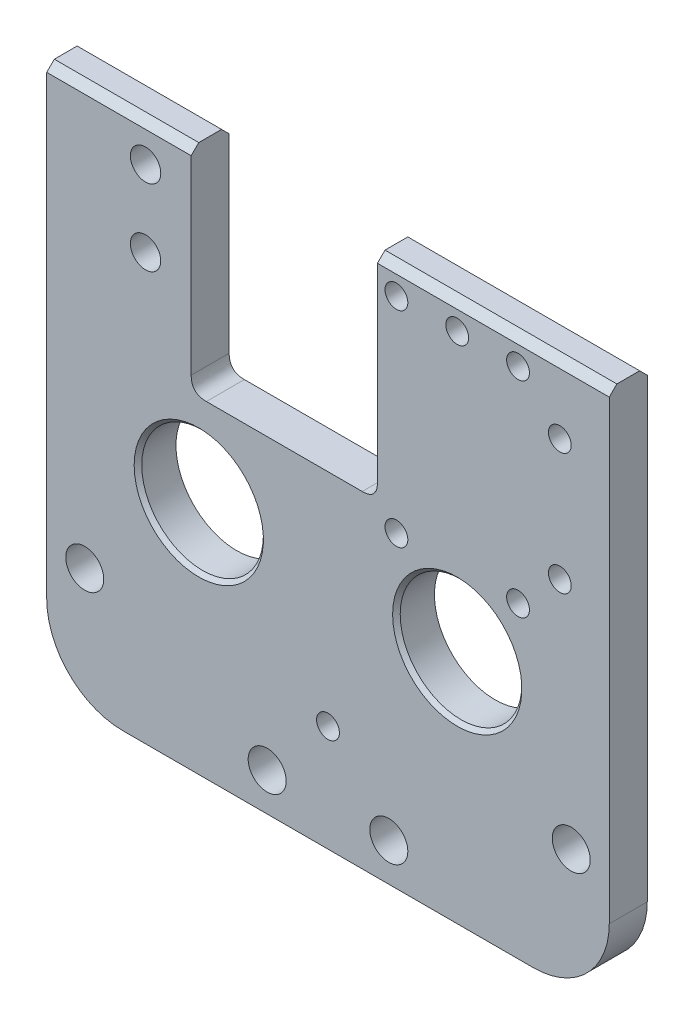
SolidWorks part; units mm, degrees
material "Stop 1060"
ref_plane "Płaszczyzna przednia" through (0, 0, 0) normal (0, 0, 1) x (1, 0, 0)
ref_plane "Płaszczyzna górna" through (0, 0, 0) normal (0, 1, 0) x (1, 0, 0)
ref_plane "Płaszczyzna prawa" through (0, 0, 0) normal (1, 0, 0) x (0, 0, -1)
sketch "Szkic1" plane through (0, 0, 0) normal (0, 0, 1) x (1, 0, 0)
  line L2 (34, 36) -> (34, -35)
  line L3 (34, -35) -> (-20, -35)
  line L6 (-20, -35) -> (-20, 36)
  line L7 (-20, 36) -> (34, 36)
  dimension "D1" = 71
  dimension "D2" = 20
  dimension "D3" = 54
  dimension "D4" = 36
extrude "Dodanie-wyciągnięcie1" add sketch "Szkic1" along normal blind 5
sketch "Szkic2" plane through (0, 0, 5) normal (0, 0, 1) x (1, 0, 0)
  line L1 (-20, 36) -> (3.5, 36)
  line L2 (-20, 36) -> (-20, 8)
  line L3 (-20, 8) -> (3.5, 8)
  line L4 (3.5, 36) -> (3.5, 8)
  dimension "D1" = 28
  dimension "D2" = 23.5
extrude "Wytnij-wyciągnięcie1" cut sketch "Szkic2" against normal blind 5
sketch "Szkic3" plane through (0, 0, 0) normal (0, 0, -1) x (-1, 0, 0)
  line L0 (-3.5, 8) -> (-3.5, 36) construction
  line L1 (-3.5, 30.5) -> (-24.5, 30.5)
  line L2 (-3.5, 30.5) -> (-3.5, 9.5)
  line L3 (-3.5, 9.5) -> (-24.5, 9.5)
  line L4 (-24.5, 30.5) -> (-24.5, 9.5)
  line L5 (-34, 36) -> (-3.5, 36) construction
  dimension "D1" = 5.5
  dimension "D2" = 21
  dimension "D3" = 21
extrude "Wytnij-wyciągnięcie2" cut sketch "Szkic3" against normal blind 3
sketch "Szkic4" plane through (0, 0, 5) normal (0, 0, 1) x (1, 0, 0)
  line L0 (3.5, 8) -> (3.5, 36) construction
  line L1 (34, 36) -> (3.5, 36) construction
  circle A0 centre (6, 32.5) radius 1.5
  circle A1 centre (14, 32.5) radius 1.5
  circle A2 centre (22, 32.5) radius 1.5
  circle A4 centre (22, 5.5) radius 1.5
  circle A5 centre (6, 5.5) radius 1.5
  circle A6 centre (27.5, 27) radius 1.5
  circle A7 centre (27.5, 11) radius 1.5
  circle A8 centre (14, 5.5) radius 1.5 [skipped]
  dimension "D1" = 2.5
  dimension "D2" = 3
  dimension "D4" = 3
  dimension "D6" = 8
  dimension "D8" = 5.5
  dimension "D10" = 3
  dimension "D3" = 3.5
  dimension "D5" = 2
  dimension "D7" = 27
  dimension "D9" = 5.5
  dimension "D11" = 2
extrude "Wytnij-wyciągnięcie3" cut sketch "Szkic4" against normal blind 5
sketch "Szkic5" plane through (0, 0, 5) normal (0, 0, 1) x (1, 0, 0)
  line L1 (-20, 8) -> (-40, 8)
  line L2 (-20, 8) -> (-20, -35)
  line L3 (-20, -35) -> (-40, -35)
  line L4 (-40, 8) -> (-40, -35)
  dimension "D1" = 20
  dimension "D2" = 43
extrude "Dodanie-wyciągnięcie2" add sketch "Szkic5" against normal blind 5
sketch "Szkic6" plane through (0, 0, 5) normal (0, 0, 1) x (1, 0, 0)
  line L0 (-40, 8) -> (-40, -35) construction
  line L1 (-40, 8) -> (3.5, 8) construction
  circle A0 centre (-20, -4) radius 8
  circle A1 centre (14, -4) radius 8
  dimension "D1" = 20
  dimension "D3" = 16
  dimension "D2" = 12
  dimension "D5" = 34
  dimension "D4" = 2
extrude "Wytnij-wyciągnięcie4" cut sketch "Szkic6" against normal blind 5
sketch "symetria" plane through (0, 0, 5) normal (0, 0, 1) x (1, 0, 0)
  line L0 (-20, -4) -> (14, -4)
  line L1 (-3, -4) -> (-3, -39)
  dimension "D1" = 35
sketch "Szkic7" plane through (0, 0, 5) normal (0, 0, 1) x (1, 0, 0)
  line L0 (-3, -4) -> (-3, -39) construction
  line L1 (-40, -35) -> (34, -35) construction
  line L2 (-3, -36.4153) -> (-3, -30)
  line L3 (-40, 8) -> (-40, -35) construction
  circle A0 centre (5, -30) radius 2.5
  circle A1 centre (-11, -30) radius 2.5
  circle A2 centre (-35, -19) radius 2.5
  circle A3 centre (29, -19) radius 2.5
  dimension "D1" = 5
  dimension "D4" = 5
  dimension "D2" = 8
  dimension "D3" = 5
  dimension "D5" = 5
  dimension "D6" = 16
extrude "Wytnij-wyciągnięcie5" cut sketch "Szkic7" against normal blind 10 contours A1 | A0 | A2 | A3 region at (5, -30, 5) region at (-11, -30, 5) region at (-35, -19, 5) region at (29, -19, 5)
fillet "Zaokrąglenie3" radius 10 2 edges at (34, -35, 2.5) (-40, -35, 2.5)
sketch "Szkic8" plane through (0, 0, 5) normal (0, 0, 1) x (1, 0, 0)
  line L1 (-40, 8) -> (-21, 8)
  line L2 (-40, 8) -> (-40, 36)
  line L3 (-40, 36) -> (-21, 36)
  line L4 (-21, 8) -> (-21, 36)
  dimension "D1" = 19
  dimension "D2" = 28
extrude "Dodanie-wyciągnięcie3" add sketch "Szkic8" against normal blind 5
fillet "Zaokrąglenie2" radius 2 2 edges at (3.5, 8, 2.5) (-21, 8, 2.5) conic rho 0.5
sketch "Szkic9" plane through (0, 0, 5) normal (0, 0, 1) x (1, 0, 0)
  line L2 (-21, 10) -> (-21, 36) construction
  line L3 (-21, 36) -> (-40, 36) construction
  circle A1 centre (-27, 31) radius 2
  circle A2 centre (-27, 21) radius 2
  dimension "D1" = 6
  dimension "D2" = 6
  dimension "D3" = 4
  dimension "D4" = 4
  dimension "D6" = 10
  dimension "D5" = 5
extrude "Wytnij-wyciągnięcie6" cut sketch "Szkic9" against normal blind 10
chamfer "Sfazowanie2" distance 1 angle 45 4 edges at (18.75, 36, 5) (18.75, 36, 0) (-30.5, 36, 0) (-30.5, 36, 5)
chamfer "Sfazowanie3" distance 0.5 angle 45 2 edges at (-12, -4, 5) (22, -4, 5)
sketch "Szkic10" plane through (0, 0, 5) normal (0, 0, 1) x (1, 0, 0)
  line L0 (-3, -4) -> (-3, -39) construction
  line L1 (-30, -35) -> (24, -35) construction
  circle A0 centre (-3, -21) radius 1.5
  dimension "D1" = 14
  dimension "D2" = 3
extrude "Wytnij-wyciągnięcie7" cut sketch "Szkic10" against normal blind 10
